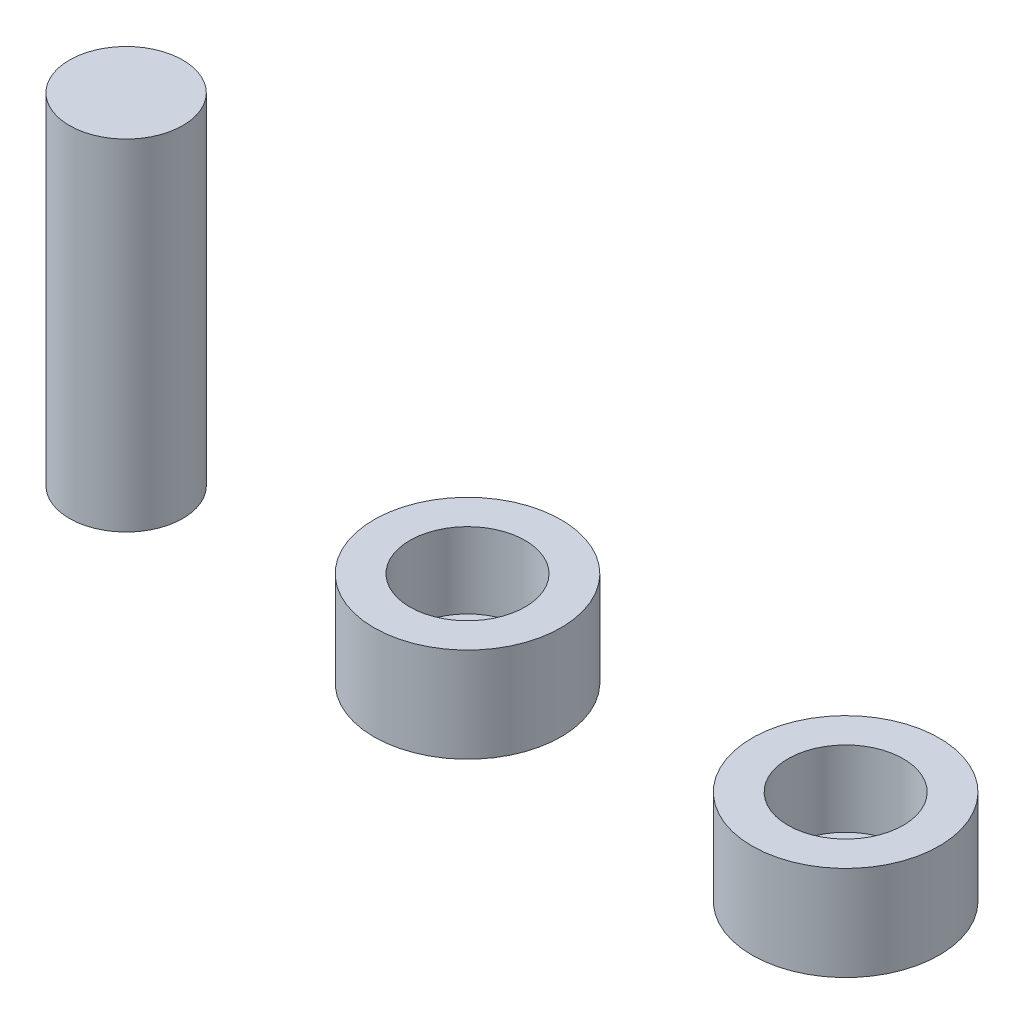
SolidWorks part; units mm, degrees
ref_plane "Front Plane" through (0, 0, 0) normal (0, 0, 1) x (1, 0, 0)
ref_plane "Top Plane" through (0, 0, 0) normal (0, 1, 0) x (1, 0, 0)
ref_plane "Right Plane" through (0, 0, 0) normal (1, 0, 0) x (0, 0, -1)
sketch "Sketch1" plane through (0, 0, 0) normal (0, 1, 0) x (1, 0, 0)
  line L0 (-9.6635, 0) -> (10.2555, 0) construction
  circle A0 centre (0, 0) radius 2.475
  point P5 (0, 0)
  dimension "D1" = 4.95
extrude "Boss-Extrude1" add sketch "Sketch1" along normal blind 2.5
sketch "Sketch2" plane through (0, 0, 0) normal (0, 1, 0) x (1, 0, 0)
  line L0 (-13.1071, 0) -> (16.2343, 0) construction
  circle A0 centre (-9.0273, 0) radius 1.5
  dimension "D1" = 3
extrude "Boss-Extrude2" add sketch "Sketch2" along normal blind 9 separate body contours A0
sketch "Sketch4" plane through (0, 2.5, 0) normal (0, 1, 0) x (1, 0, 0)
  line L0 (-2.5821, 0) -> (3.9052, 0) construction
  circle A0 centre (0, 0) radius 1.525
  point P5 (0, 0)
  point P6 (0, 0)
  dimension "D1" = 3.05
extrude "Cut-Extrude1" cut sketch "Sketch4" against normal blind 2
ref_plane "Plane1" through (5, 0, 0) normal (1, 0, 0) x (0, 0, -1)
mirror "Mirror1" about plane through (5, 0, 0) normal (1, 0, 0) of bodies 104 101
